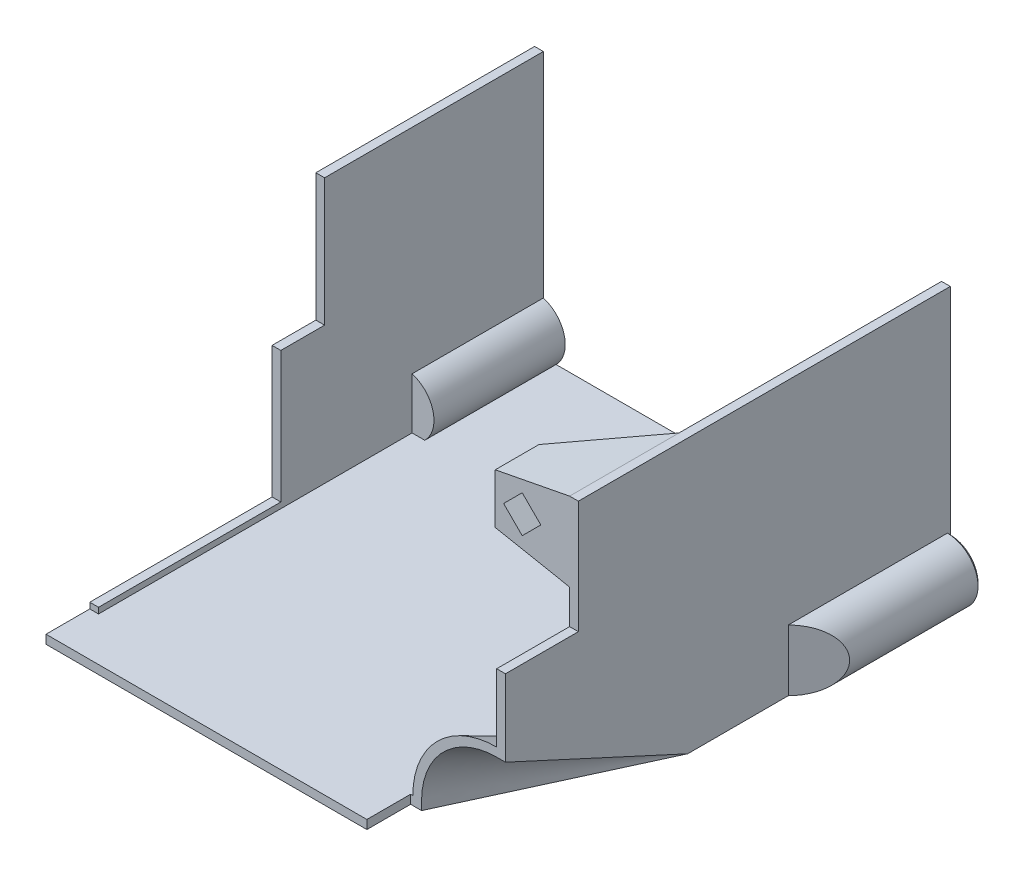
SolidWorks part; units mm, degrees
material "Custom Plastic"
ref_plane "Front Plane" through (0, 0, 0) normal (0, 0, 1) x (1, 0, 0)
ref_plane "Top Plane" through (0, 0, 0) normal (0, 1, 0) x (1, 0, 0)
ref_plane "Right Plane" through (0, 0, 0) normal (1, 0, 0) x (0, 0, -1)
sketch "Sketch1" plane through (0, 0, 0) normal (0, 0, 1) x (1, 0, 0)
  line L1 (-33.6475, 16.5475) -> (-34.8475, 16.5475)
  line L2 (-33.6475, -19.7525) -> (-33.6475, -20.9525) construction
  line L3 (-31.9081, -19.7525) -> (19.2131, -19.7525)
  line L4 (20.9525, 16.5475) -> (20.9525, -12.7276)
  line L5 (-33.6475, -12.7276) -> (-33.6475, 16.5475)
  line L7 (20.9525, 16.5475) -> (22.1525, 16.5475)
  line L8 (-34.8475, 16.5475) -> (-34.8475, -12.5525)
  line L9 (-34.8475, -20.9525) -> (22.1525, -20.9525)
  line L10 (22.1525, 16.5475) -> (22.1525, -12.5525)
  arc A0 (22.1525, -20.9525) -> (22.1525, -12.5525) centre (22.1525, -16.7525) ccw
  circle A1 centre (22.1525, -16.7525) radius 1.6 construction
  arc A2 (20.9525, -12.7276) -> (19.2131, -19.7525) centre (22.1525, -16.7525) ccw
  circle A3 centre (-34.8475, -16.7525) radius 1.6 construction
  arc A4 (-34.8475, -12.5525) -> (-34.8475, -20.9525) centre (-34.8475, -16.7525) ccw
  arc A6 (-31.9081, -19.7525) -> (-33.6475, -12.7276) centre (-34.8475, -16.7525) ccw
  dimension "D2" = 3.2
  dimension "D5" = 4.2
  dimension "D1" = 1.2
  dimension "D3" = 57
  dimension "D4" = 37.5
extrude "Boss-Extrude1" add sketch "Sketch1" along normal blind 67
sketch "Sketch2" plane through (0, 0, 67) normal (0, 0, 1) x (1, 0, 0)
  line L0 (-34.8475, -20.9525) -> (22.1525, -20.9525) construction
  line L1 (9.1525, -20.9525) -> (32.8781, -20.9525)
  line L2 (9.1525, -20.9525) -> (9.1525, -19.7525)
  line L3 (-34.8475, 12.6741) -> (32.8781, 12.6741)
  line L4 (32.8781, -20.9525) -> (32.8781, 12.6741)
  line L5 (22.1525, -12.5525) -> (22.1525, 16.5475) construction
  line L6 (9.1525, -19.7525) -> (-34.8475, -19.7525)
  line L7 (19.2131, -19.7525) -> (-31.9081, -19.7525) construction
  line L8 (-34.8475, 16.5475) -> (-34.8475, -12.5525) construction
  line L9 (-34.8475, -20.9525) -> (-34.8475, -19.7525)
  line L10 (-34.8475, -20.9525) -> (-42.7406, -20.9525)
  line L11 (-34.8475, -20.9525) -> (22.1525, -20.9525) construction
  line L12 (-42.7406, -20.9525) -> (-42.7406, -7.5075)
  line L13 (-42.7406, -7.5075) -> (-34.8475, -7.5075)
  line L14 (-34.8475, -7.5075) -> (-34.8475, 12.6741)
  dimension "D1" = 13
extrude "Cut-Extrude1" cut sketch "Sketch2" against normal blind 6
sketch "Sketch3" plane through (0, 0, 61) normal (0, 0, 1) x (1, 0, 0)
  line L0 (22.1525, -12.5525) -> (22.1525, 12.6741) construction
  line L1 (-34.8475, 16.5475) -> (22.1525, 16.5475)
  line L2 (-34.8475, 16.5475) -> (-34.8475, 1.0475)
  line L3 (-34.8475, 1.0475) -> (22.1525, 1.0475)
  line L4 (22.1525, 16.5475) -> (22.1525, 1.0475)
  dimension "D1" = 15.5
extrude "Cut-Extrude2" cut sketch "Sketch3" against normal blind 10 and the other way blind 10
sketch "Sketch4" plane through (0, 0, 51) normal (0, 0, 1) x (1, 0, 0)
  line L0 (-34.8475, 16.5475) -> (-34.8475, 1.0475) construction
  line L1 (-34.8475, 16.5475) -> (-33.6475, 16.5475)
  line L2 (-34.8475, 16.5475) -> (-34.8475, -0.9525)
  line L3 (-34.8475, -0.9525) -> (-33.6475, -0.9525)
  line L4 (-33.6475, 16.5475) -> (-33.6475, -0.9525)
extrude "Cut-Extrude3" cut sketch "Sketch4" against normal blind 21
sketch "Sketch6" plane through (0, 0, 0) normal (0, 0, -1) x (-1, 0, 0)
  circle A0 centre (-22.1525, -16.7525) radius 1.5
  circle A1 centre (34.8475, -16.7525) radius 1.5
  arc A2 (34.8475, -20.9525) -> (34.8475, -12.5525) centre (34.8475, -16.7525) ccw construction
  arc A3 (-22.1525, -12.5525) -> (-22.1525, -20.9525) centre (-22.1525, -16.7525) ccw construction
  dimension "D1" = 3
extrude "Cut-Extrude4" cut sketch "Sketch6" against normal blind 16
sketch "Sketch7" plane through (0, 0, 61) normal (0, 0, 1) x (1, 0, 0)
  line L0 (19.2131, -19.7525) -> (9.1525, -19.7525) construction
  line L1 (22.1525, -12.5525) -> (31.8181, -12.5525)
  line L2 (22.1525, -12.5525) -> (22.1525, -20.9525)
  line L3 (22.1525, -20.9525) -> (31.8181, -20.9525)
  line L4 (31.8181, -12.5525) -> (31.8181, -20.9525)
  line L5 (20.9525, -12.7276) -> (15.0843, -12.7276)
  line L6 (20.9525, -12.7276) -> (20.9525, -19.7525)
  line L7 (20.9525, -19.7525) -> (15.0843, -19.7525)
  line L8 (15.0843, -12.7276) -> (15.0843, -19.7525)
  line L9 (-33.6475, -12.7276) -> (-33.6475, 1.0475) construction
  line L10 (-34.8475, -20.9525) -> (-44.0251, -20.9525)
  line L11 (-34.8475, -20.9525) -> (-34.8475, -7.6032)
  line L12 (-34.8475, -7.6032) -> (-44.0251, -7.6032)
  line L13 (-44.0251, -20.9525) -> (-44.0251, -7.6032)
  line L14 (-33.6475, -7.6032) -> (-26.816, -7.6032)
  line L15 (-33.6475, -7.6032) -> (-33.6475, -19.7525)
  line L16 (-33.6475, -19.7525) -> (-26.816, -19.7525)
  line L17 (-26.816, -7.6032) -> (-26.816, -19.7525)
  line L18 (9.1525, -19.7525) -> (-34.8475, -19.7525) construction
extrude "Cut-Extrude5" cut sketch "Sketch7" against normal offset from surface (43 mm away) 18 up to face at (-36.3475, -16.7525, 0)
chamfer "Chamfer1" distance 4.2 angle 45 2 edges at (22.1525, -16.7525, 18) (-34.8475, -16.7525, 18)
chamfer "Chamfer3" distance 0.6 angle 30 2 edges at (20.6525, -16.7525, 0) (-36.3475, -16.7525, 0) first distance on face at (20.6525, -16.7525, 16) first distance on face at (-36.3475, -16.7525, 16)
chamfer "Chamfer4" distance 0.4 angle 45 3 edges at (-39.0475, -16.7525, 0) (-6.3475, -20.9525, 0) (26.3525, -16.7525, 0)
sketch "Sketch8" plane through (0, 0, 51) normal (0, 0, 1) x (1, 0, 0)
  line L0 (14.4525, 12.7475) -> (10.7525, 12.7475) construction
  line L1 (11.9025, 11.1475) -> (14.4525, 13.6975)
  line L2 (10.7525, 9.5475) -> (14.4525, 9.5475) construction
  line L4 (10.7525, 14.5725) -> (10.7525, 12.7475)
  line L5 (10.7525, 9.5475) -> (10.7525, 7.7225)
  line L7 (20.9525, 16.5475) -> (20.9525, 1.0475) construction
  line L8 (20.9525, 5.7475) -> (22.1525, 5.7475)
  line L9 (22.1525, 1.0475) -> (22.1525, 16.5475) construction
  line L10 (22.1525, 5.7475) -> (22.1525, 16.5475)
  line L11 (22.1525, 16.5475) -> (20.9525, 16.5475)
  line L12 (11.9025, 11.1475) -> (14.4525, 8.5975)
  line L13 (14.4525, 13.6975) -> (17.0025, 11.1475)
  line L14 (14.4525, 8.5975) -> (17.0025, 11.1475)
  line L15 (11.9025, 11.1475) -> (22.1525, 11.1475) construction
  line L16 (14.4525, 13.6975) -> (14.4525, 8.5975) construction
  line L17 (10.7525, 12.7475) -> (10.7525, 9.5475)
  line L18 (20.9525, 16.5475) -> (10.7525, 14.5725)
  line L19 (20.9525, 5.7475) -> (10.7525, 7.7225)
  arc A0 (14.4525, 9.5475) -> (14.4525, 12.7475) centre (14.4525, 11.1475) ccw construction
  circle A1 centre (14.4525, 11.1475) radius 2.55 construction
  dimension "D1" = 1.6
  dimension "D5" = 5.1
  dimension "D2" = 6.5
  dimension "D3" = 5.4
  dimension "D4" = 10.2
  dimension "D6" = 6.85
extrude "Boss-Extrude2" add sketch "Sketch8" against normal blind 15
sketch "Sketch10" plane through (0, 0, 36) normal (0, 0, -1) x (-1, 0, 0)
  line L0 (-14.4525, 14.1475) -> (-10.7525, 14.1475)
  line L1 (-10.7525, 14.5725) -> (-10.7525, 7.7225) construction
  line L2 (-10.7525, 14.1475) -> (-10.7525, 8.1475)
  line L3 (-10.7525, 8.1475) -> (-14.4525, 8.1475)
  line L5 (-14.4525, 13.6975) -> (-14.4525, 8.5975) construction
  arc A0 (-14.4525, 14.1475) -> (-14.4525, 8.1475) centre (-14.4525, 11.1475) ccw
  arc A1 (-14.4525, 8.1475) -> (-14.4525, 14.1475) centre (-14.4525, 11.1475) ccw construction
  dimension "D1" = 3
extrude "Cut-Extrude6" cut sketch "Sketch10" against normal offset from surface 6 and the other way blind 10 up to face at (18.3811, 9.0332, 51)
sketch "Sketch11" plane through (0, 16.5475, 0) normal (0, 1, 0) x (1, 0, 0)
  line L0 (20.9525, -36) -> (10.7525, -45)
  line L1 (10.7525, -36) -> (10.7525, -51) construction
  line L2 (10.7525, -45) -> (10.7525, -36)
  line L3 (10.7525, -36) -> (20.9525, -36)
extrude "Cut-Extrude7" cut sketch "Sketch11" against normal up to surface and the other way blind 10 up to face at (15.8525, 6.735, 43.5)
sketch "Sketch12" plane through (0, 1.0475, 0) normal (0, 1, 0) x (1, 0, 0)
  line L0 (-34.8475, -61) -> (-34.8475, -51) construction
  line L1 (-34.8475, -36) -> (-33.6475, -36)
  line L2 (-34.8475, -36) -> (-34.8475, -61)
  line L3 (-34.8475, -61) -> (-33.6475, -61)
  line L4 (-33.6475, -36) -> (-33.6475, -61)
  line L5 (-33.6475, -30) -> (-34.8475, -30) construction
  point P7 (-34.2475, -30)
  dimension "D1" = 6
extrude "Cut-Extrude8" cut sketch "Sketch12" against normal offset from surface (20 mm away) 0.8 up to face at (-8.5141, -19.7525, 37.5)
sketch "Sketch13" plane through (0, 0, 61) normal (0, 0, 1) x (1, 0, 0)
  line L0 (20.9525, 1.0475) -> (20.9525, -19.7525) construction
  line L1 (20.9525, -19.7525) -> (9.1525, -19.7525) construction
  line L2 (9.4525, -19.7525) -> (20.9525, -19.7525)
  line L3 (20.9525, -19.7525) -> (20.9525, -8.2525)
  arc A0 (20.9525, -8.2525) -> (9.4525, -19.7525) centre (20.9525, -19.7525) ccw
  dimension "D1" = 11.5
sketch "Sketch14" plane through (20.9525, 0, 0) normal (-1, 0, 0) x (0, 0, 1)
  line L0 (18, -19.7525) -> (61, -19.7525) construction
  line L1 (61, 1.0475) -> (61, -19.7525) construction
  point P0 (36, -19.7525)
  dimension "D1" = 25
loft "Loft1" add profiles "Sketch13", "Sketch14"
sketch "Sketch15" plane through (0, 0, 61) normal (0, 0, 1) x (1, 0, 0)
  line L2 (20.9525, -9.4525) -> (22.1525, -9.4525)
  line L4 (22.1525, -20.9525) -> (22.1525, -12.5525) construction
  line L5 (22.1525, -9.4525) -> (22.1525, -20.9525)
  line L6 (22.1525, -20.9525) -> (10.6525, -20.9525)
  line L7 (9.1525, -20.9525) -> (22.1525, -20.9525) construction
  line L8 (10.6525, -20.9525) -> (10.6525, -19.7525)
  line L9 (20.9525, -9.4525) -> (20.9525, -8.2525) construction
  line L10 (20.9525, -8.2525) -> (22.1525, -8.2525) construction
  line L11 (22.1525, -20.9525) -> (22.1525, 1.0475) construction
  arc A0 (20.9525, -9.4525) -> (10.6525, -19.7525) centre (20.9525, -19.7525) ccw
  arc A1 (22.1525, -20.9525) -> (26.3525, -16.7525) centre (22.1525, -16.7525) ccw construction
sketch "Sketch16" plane through (22.1525, 0, 0) normal (1, 0, 0) x (0, 0, -1)
  line L0 (-61, -20.9525) -> (-22.2, -20.9525) construction
  point P0 (-36, -20.9525)
loft "Cut-Loft1" cut profiles "Sketch15", "Sketch16"
equation "\"y-cross-rib-thickness\"=6"
equation "\"y-rib-thickness\"=6"
equation "\"bed-plate-thickness\"=6"
equation "\"x-plate-thickness\"=5"
equation "\"rod-diameter\"=12"
equation "\"t-nut-hole-diameter\"=3"
equation "\"y-plate-thickness\"=5"
equation "\"enclosure-thickness\"=0.6"
equation "\"M3-Clearance\"=3.3"
equation "\"M4-Clearance\"=4.3"
equation "\"M5-Clearance\"=5.3"
equation "\"M6-Clearance\"=6.3"
equation "\"M8-Clearance\"=8.3"
equation "\"623-Bearing-Dia\"=11.2"
